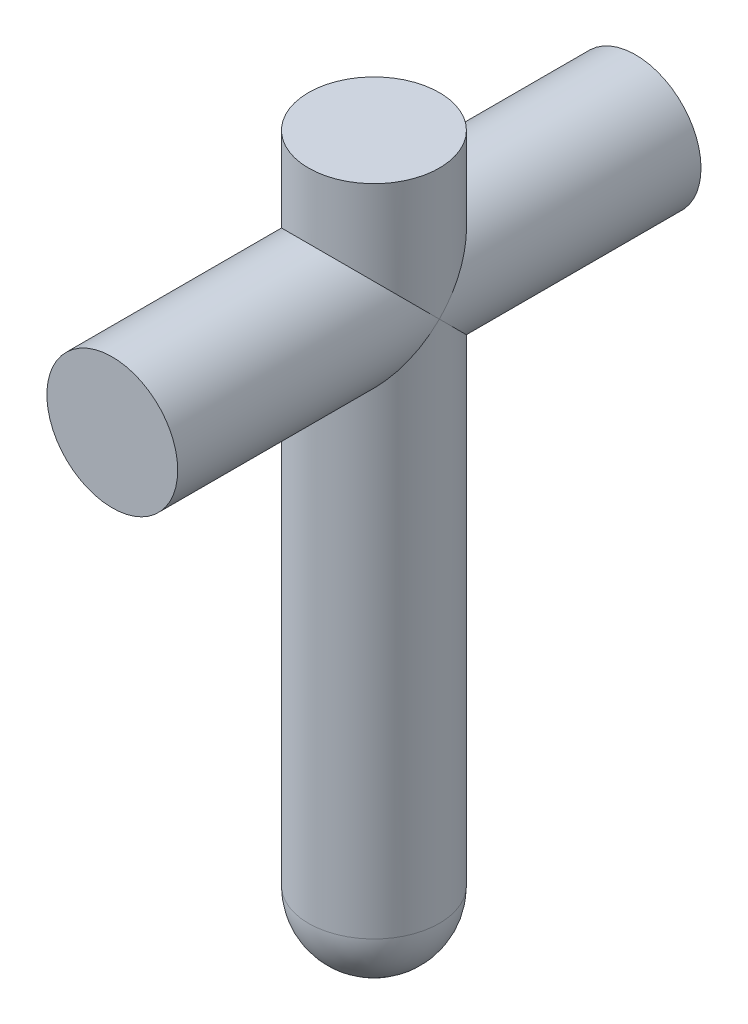
SolidWorks part; units mm, degrees
ref_plane "Front Plane" through (0, 0, 0) normal (0, 0, 1) x (1, 0, 0)
ref_plane "Top Plane" through (0, 0, 0) normal (0, 1, 0) x (1, 0, 0)
ref_plane "Right Plane" through (0, 0, 0) normal (1, 0, 0) x (0, 0, -1)
sketch "Sketch1" plane through (0, 0, 0) normal (0, 1, 0) x (1, 0, 0)
  circle A0 centre (0, 0) radius 3.175
extrude "Boss-Extrude1" add sketch "Sketch1" along normal blind 31.75
sketch "Sketch2" plane through (0, 0, 0) normal (0, 0, 1) x (1, 0, 0)
  circle A0 centre (0, 25.4) radius 3.175
  dimension "D1" = 25.4
extrude "Boss-Extrude2" add sketch "Sketch2" along normal mid plane 25.4
dome "Dome2" faces to dome 1 distance 3.175 reverse direction no elliptical dome no face at (0, 0, 3.175) parameters "D1"=3.175
